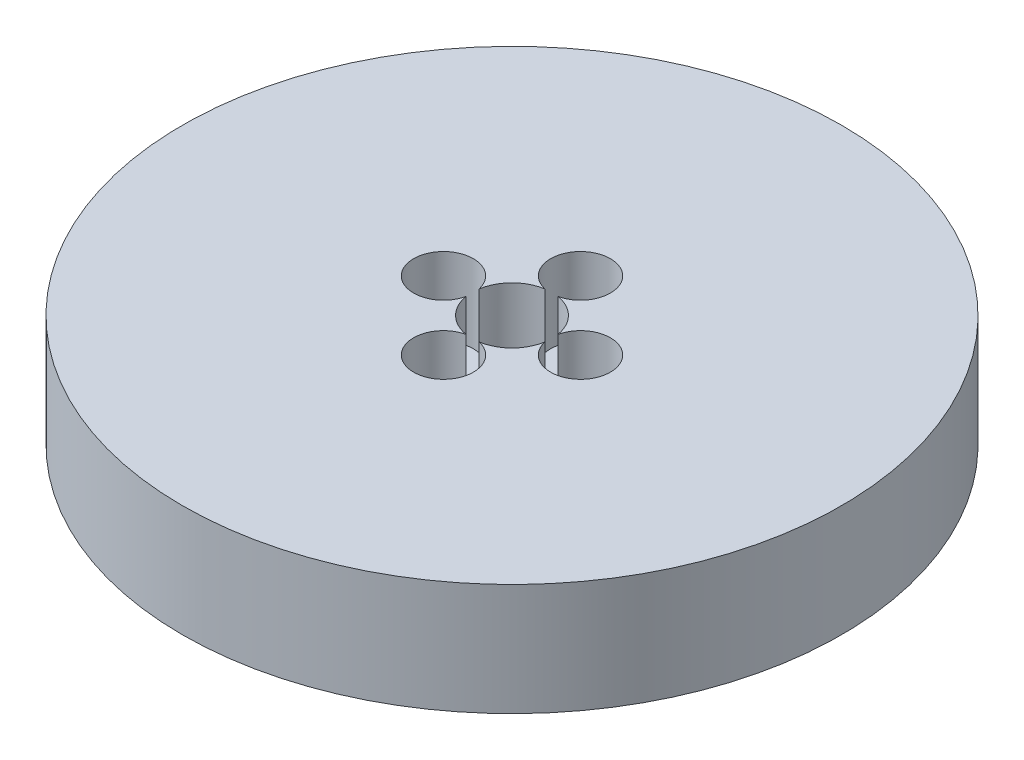
SolidWorks part; units mm, degrees
ref_plane "Front Plane" through (0, 0, 0) normal (0, 0, 1) x (1, 0, 0)
ref_plane "Top Plane" through (0, 0, 0) normal (0, 1, 0) x (1, 0, 0)
ref_plane "Right Plane" through (0, 0, 0) normal (1, 0, 0) x (0, 0, -1)
sketch "Sketch1" plane through (0, 0, 0) normal (0, 1, 0) x (1, 0, 0)
  circle A0 centre (0, 0) radius 82.5
  dimension "FLANGE_OD" = 165
extrude "Boss-Extrude1" add sketch "Sketch1" along normal blind 28
sketch "Sketch2" plane through (0, 0, 0) normal (0, 1, 0) x (1, 0, 0)
  circle A0 centre (0, 0) radius 10
  dimension "BORE_D" = 20
extrude "Cut-Extrude1" cut sketch "Sketch2" along normal through all
sketch "Sketch3" plane through (0, 28, 0) normal (0, 1, 0) x (1, 0, 0)
  circle A0 centre (0, 0) radius 17.1515 construction
  circle A1 centre (-17.1515, 0) radius 7.4748
  dimension "BOLT_D" = 14.9497
  dimension "BOLT_PCD" = 34.303
extrude "Cut-Extrude2" cut sketch "Sketch3" against normal blind 19.5383
pattern_circular "CirPattern1" count 4 over 360 about axis through (0, 0, 0) along (0, 1, 0) of "Cut-Extrude2"
